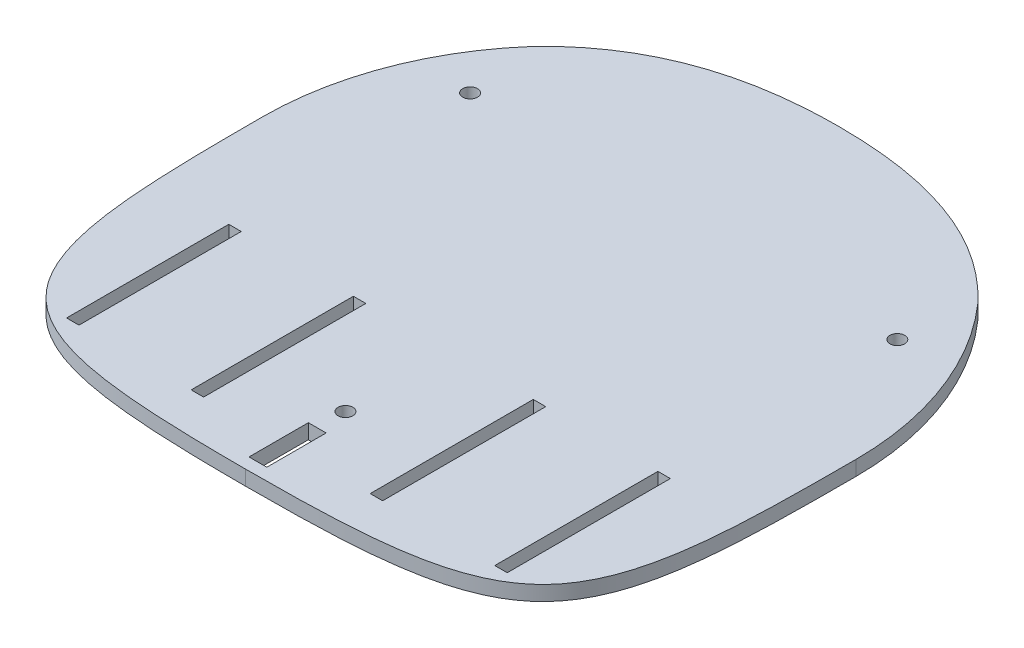
SolidWorks part; units mm, degrees
ref_plane "Front Plane" through (0, 0, 0) normal (0, 0, 1) x (1, 0, 0)
ref_plane "Top Plane" through (0, 0, 0) normal (0, 1, 0) x (1, 0, 0)
ref_plane "Right Plane" through (0, 0, 0) normal (1, 0, 0) x (0, 0, -1)
sketch "Layer1Limits" plane through (0, 0, 0) normal (0, 1, 0) x (1, 0, 0)
  line L0 (-127, 119.8228) -> (127, -134.1772) construction
  line L1 (-127, -134.1772) -> (127, -134.1772) construction
  line L2 (-127, -134.1772) -> (-127, 119.8228) construction
  line L3 (-127, 119.8228) -> (127, 119.8228) construction
  line L4 (127, -134.1772) -> (127, 119.8228) construction
  line L5 (127, 119.8228) -> (-127, -134.1772) construction
  line L6 (0, -1000) -> (0, 49000) construction
  point P4 (0, -7.1772)
  dimension "D1" = 254
  dimension "D2" = 254
sketch "Sketch1" plane through (0, 0, 0) normal (0, 1, 0) x (1, 0, 0)
  line L0 (0, 0) -> (-157.9039, -157.9039) construction
  line L1 (0, -134.1772) -> (0, 127) construction
  line L2 (-127, -134.1772) -> (127, -134.1772) construction
  arc A0 (127, 0) -> (-127, 0) centre (0, 0) ccw
  spline S0 degree 3 poles (-127, 0) (-127, -50.6247) (-125.8471, -127.4032) (-59.0891, -134.1772) (0, -134.1772) knots 0 0 0 0 0.496988 1 1 1 1
  spline S1 degree 3 poles (127, 0) (127, -50.6247) (125.8471, -127.4032) (59.0891, -134.1772) (0, -134.1772) knots 0 0 0 0 0.496988 1 1 1 1
  dimension "D1" = 254
extrude "Base" add sketch "Sketch1" along normal blind 6.35
sketch "Sketch16" plane through (0, 6.35, 0) normal (0, 1, 0) x (1, 0, 0)
  line L0 (0, -1000) -> (0, 49000) construction
  line L1 (-95.2696, 133.35) -> (-95.2696, 83.9803)
  line L2 (-95.2696, 133.35) -> (95.2696, 133.35)
  line L3 (95.2696, 133.35) -> (95.2696, 83.9803)
  arc A0 (127, 0) -> (-127, 0) centre (0, 0) ccw construction
  spline S0 degree 3 poles (-95.2696, 83.9803) (-69.156, 111.7112) (-34.9729, 119.8228) (0, 119.8228) knots 0 0 0 0 1 1 1 1
  spline S1 degree 3 poles (95.2696, 83.9803) (69.156, 111.7112) (34.9729, 119.8228) (0, 119.8228) knots 0 0 0 0 1 1 1 1
extrude "EmptySpaceTrim" cut sketch "Sketch16" against normal through all
sketch "ShaftLayout" plane through (0, 6.35, 0) normal (0, 1, 0) x (1, 0, 0)
  line L0 (-127, 0) -> (127, 0) construction
  line L1 (0, 133.35) -> (0, -127) construction
  line L2 (-114.7053, -6.35) -> (-104.7993, -6.35)
  line L3 (-36.3853, -38) -> (-94.3853, -38)
  line L4 (-36.3853, -38) -> (-36.3853, 38)
  line L5 (-36.3853, 38) -> (-94.3853, 38)
  line L6 (-94.3853, -38) -> (-94.3853, 38)
  line L7 (-36.3853, -38) -> (-94.3853, 38) construction
  line L8 (-36.3853, 38) -> (-94.3853, -38) construction
  line L9 (-102.0053, -15.875) -> (-104.7993, -15.875)
  line L10 (-102.0053, -15.875) -> (-102.0053, 15.875)
  line L11 (-102.0053, 15.875) -> (-104.7993, 15.875)
  line L12 (-104.7993, -15.875) -> (-104.7993, 15.875)
  line L13 (-102.0053, -15.875) -> (-104.7993, 15.875) construction
  line L14 (-102.0053, 15.875) -> (-104.7993, -15.875) construction
  line L15 (-114.7053, -6.35) -> (-114.7053, 6.35)
  line L16 (-104.7993, -6.35) -> (-104.7993, 6.35)
  line L17 (-114.7053, 6.35) -> (-104.7993, 6.35)
  line L18 (-114.7053, -6.35) -> (-104.7993, 6.35) construction
  line L19 (-104.7993, -6.35) -> (-114.7053, 6.35) construction
  line L20 (-116.2928, -9.525) -> (-114.7053, -9.525)
  line L21 (-116.2928, -9.525) -> (-116.2928, 9.525)
  line L22 (-114.7053, -9.525) -> (-114.7053, 9.525)
  line L23 (-116.2928, 9.525) -> (-114.7053, 9.525)
  line L24 (-116.2928, -9.525) -> (-114.7053, 9.525) construction
  line L25 (-114.7053, -9.525) -> (-116.2928, 9.525) construction
  line L26 (-127.4053, -7.9375) -> (-116.2928, -7.9375)
  line L27 (-127.4053, -7.9375) -> (-127.4053, 7.9375)
  line L28 (-116.2928, -7.9375) -> (-116.2928, 7.9375)
  line L29 (-127.4053, 7.9375) -> (-116.2928, 7.9375)
  line L30 (-127.4053, -7.9375) -> (-116.2928, 7.9375) construction
  line L31 (-116.2928, -7.9375) -> (-127.4053, 7.9375) construction
  line L32 (-17.3353, -7.9375) -> (-28.4478, -7.9375)
  line L33 (-30.0353, -9.525) -> (-28.4478, -9.525)
  line L34 (-30.0353, -9.525) -> (-30.0353, 9.525)
  line L35 (-30.0353, 9.525) -> (-28.4478, 9.525)
  line L36 (-28.4478, -9.525) -> (-28.4478, 9.525)
  line L37 (-30.0353, -9.525) -> (-28.4478, 9.525) construction
  line L38 (-30.0353, 9.525) -> (-28.4478, -9.525) construction
  line L39 (-17.3353, -7.9375) -> (-17.3353, 7.9375)
  line L40 (-28.4478, -7.9375) -> (-28.4478, 7.9375)
  line L41 (-17.3353, 7.9375) -> (-28.4478, 7.9375)
  line L42 (-17.3353, -7.9375) -> (-28.4478, 7.9375) construction
  line L43 (-28.4478, -7.9375) -> (-17.3353, 7.9375) construction
  line L45 (-67.3853, -10.033) -> (-56.3853, -10.033)
  line L46 (-67.3853, -10.033) -> (-67.3853, 10.033)
  line L47 (-67.3853, 10.033) -> (-56.3853, 10.033)
  line L48 (-56.3853, -10.033) -> (-56.3853, 10.033)
  line L49 (-67.3853, -10.033) -> (-56.3853, 10.033) construction
  line L50 (-67.3853, 10.033) -> (-56.3853, -10.033) construction
  point P10 (-65.3853, 0)
  point P15 (-103.4023, 0)
  point P20 (-29.2416, 0)
  point P21 (-109.7523, 0)
  point P22 (-115.4991, 0)
  point P23 (-121.8491, 0)
  point P40 (-61.8853, 0)
  point P41 (-22.8916, 0)
  dimension "D1" = 58
  dimension "D2" = 76
  dimension "D3" = 7.62
  dimension "D4" = 2.794
  dimension "D5" = 31.75
  dimension "D6" = 9.906
  dimension "D7" = 12.7
  dimension "D8" = 19.05
  dimension "D9" = 1.5875
  dimension "D10" = 12.7
  dimension "D11" = 15.875
  dimension "D12" = 19.05
  dimension "D13" = 1.5875
  dimension "D14" = 15.875
  dimension "D15" = 12.7
  dimension "D16" = 6.35
  dimension "D17" = 20.066
  dimension "D18" = 20
  dimension "D19" = 11
sketch "MotorLayout" plane through (0, 6.35, 0) normal (0, 1, 0) x (1, 0, 0)
  line L0 (-94.3853, -81.74) -> (-114.3853, -81.74) construction
  line L1 (-94.3853, -110.24) -> (-18.3853, -110.24)
  line L2 (-94.3853, -110.24) -> (-94.3853, -53.24)
  line L3 (-94.3853, -53.24) -> (-18.3853, -53.24)
  line L4 (-18.3853, -110.24) -> (-18.3853, -53.24)
  line L5 (-94.3853, -110.24) -> (-18.3853, -53.24) construction
  line L6 (-94.3853, -53.24) -> (-18.3853, -110.24) construction
  line L7 (-114.7053, -92.0587) -> (-104.7993, -92.0587)
  line L8 (-104.7993, -97.615) -> (-102.0053, -97.615)
  line L9 (-104.7993, -97.615) -> (-104.7993, -65.865)
  line L10 (-104.7993, -65.865) -> (-102.0053, -65.865)
  line L11 (-102.0053, -97.615) -> (-102.0053, -65.865)
  line L12 (-104.7993, -97.615) -> (-102.0053, -65.865) construction
  line L13 (-104.7993, -65.865) -> (-102.0053, -97.615) construction
  line L14 (-36.3853, -38) -> (-94.3853, -38) construction
  line L15 (-114.7053, -92.0587) -> (-114.7053, -71.4212)
  line L16 (-104.7993, -92.0587) -> (-104.7993, -71.4212)
  line L17 (-114.7053, -71.4212) -> (-104.7993, -71.4212)
  line L18 (-114.7053, -92.0587) -> (-104.7993, -71.4212) construction
  line L19 (-104.7993, -92.0587) -> (-114.7053, -71.4212) construction
  line L20 (-103.4023, -1000) -> (-103.4023, 49000) construction
  line L21 (-34.8953, -53.24) -> (-34.8953, -110.24) construction
  point P0 (-56.3853, -81.74)
  point P7 (-103.4023, -81.74)
  point P14 (-109.7523, -81.74)
  dimension "D1" = 20
  dimension "D2" = 76
  dimension "D3" = 57
  dimension "D4" = 2.794
  dimension "D5" = 15.24
  dimension "D6" = 31.75
  dimension "D7" = 20.6375
  dimension "D8" = 12.7
  dimension "D9" = 7.62
  dimension "D10" = 16.51
sketch "Sketch8" plane through (0, 6.35, 0) normal (0, 1, 0) x (1, 0, 0)
  line L0 (-94.3853, -81.74) -> (-18.3853, -81.74) construction
  line L1 (-18.3853, -110.24) -> (-18.3853, -53.24) construction
  line L2 (-94.3853, -53.24) -> (-18.3853, -53.24) construction
  line L3 (-35.7113, -116.463) -> (-41.0453, -116.463)
  line L4 (-35.7113, -116.463) -> (-35.7113, -47.017)
  line L5 (-35.7113, -47.017) -> (-41.0453, -47.017)
  line L6 (-41.0453, -116.463) -> (-41.0453, -47.017)
  line L7 (-35.7113, -116.463) -> (-41.0453, -47.017) construction
  line L8 (-35.7113, -47.017) -> (-41.0453, -116.463) construction
  line L9 (0, -1000) -> (0, 49000) construction
  line L10 (-94.3853, -110.24) -> (-18.3853, -110.24) construction
  line L11 (-3.81, -128.9302) -> (3.81, -128.9302)
  line L12 (89.0513, -46.763) -> (94.3853, -116.59) construction
  line L13 (89.0513, -116.59) -> (94.3853, -46.763) construction
  line L14 (35.7113, -46.763) -> (41.0453, -116.59) construction
  line L15 (-89.0513, -116.463) -> (-94.3853, -116.463)
  line L16 (-89.0513, -116.463) -> (-89.0513, -47.017)
  line L17 (-89.0513, -47.017) -> (-94.3853, -47.017)
  line L18 (-94.3853, -116.463) -> (-94.3853, -47.017)
  line L19 (-89.0513, -116.463) -> (-94.3853, -47.017) construction
  line L20 (-89.0513, -47.017) -> (-94.3853, -116.463) construction
  line L21 (-94.3853, -110.24) -> (-94.3853, -53.24) construction
  line L22 (-3.81, -128.9302) -> (-3.81, -103.5302)
  line L23 (35.7113, -116.59) -> (41.0453, -46.763) construction
  line L24 (-3.81, -103.5302) -> (3.81, -103.5302)
  line L25 (3.81, -128.9302) -> (3.81, -103.5302)
  line L26 (-3.81, -128.9302) -> (3.81, -103.5302) construction
  line L27 (-3.81, -103.5302) -> (3.81, -128.9302) construction
  line L29 (94.3853, -116.59) -> (94.3853, -46.763)
  line L30 (89.0513, -46.763) -> (94.3853, -46.763)
  line L31 (89.0513, -116.59) -> (89.0513, -46.763)
  line L32 (89.0513, -116.59) -> (94.3853, -116.59)
  line L33 (41.0453, -116.59) -> (41.0453, -46.763)
  line L34 (35.7113, -46.763) -> (41.0453, -46.763)
  line L35 (35.7113, -116.59) -> (35.7113, -46.763)
  line L36 (35.7113, -116.59) -> (41.0453, -116.59)
  point P6 (-63.7079, -81.74)
  point P7 (-38.2513, -81.74)
  point P16 (0, -116.2302)
  point P19 (-91.5913, -81.74)
  point P39 (91.5913, -81.74)
  point P40 (38.2513, -81.74)
  dimension "D1" = 5.334
  dimension "D2" = 6.223
  dimension "D4" = 7.62
  dimension "D5" = 25.4
  dimension "D6" = 6.223
  dimension "D3" = 2
extrude "MotorCut" cut sketch "Sketch8" against normal through all
sketch "Sketch11" plane through (0, 6.35, 0) normal (0, 1, 0) x (1, 0, 0)
  line L0 (0, -1000) -> (0, 49000) construction
  line L1 (-127, 0) -> (127, 0) construction
  circle A1 centre (0, -91.44) radius 3.175
  circle A2 centre (-91.44, 53.34) radius 3.175
  circle A3 centre (91.44, 53.34) radius 3.175
  dimension "D1" = 6.35
  dimension "D2" = 91.44
  dimension "D3" = 6.35
  dimension "D6" = 91.44
  dimension "D4" = 53.34
extrude "ScrewCut" cut sketch "Sketch11" against normal through all
sketch "Sketch17" plane through (0, 6.35, 0) normal (0, 1, 0) x (1, 0, 0)
  line L0 (-94.3853, -47.017) -> (-94.3853, -116.463) construction
  line L1 (94.3853, -116.59) -> (94.3853, -46.763) construction
  line L2 (-112.1653, -34.317) -> (112.1653, -34.317) construction
  line L3 (-112.1653, -34.317) -> (-112.1653, 40.64) construction
  line L4 (-112.1653, 40.64) -> (112.1653, 40.64) construction
  line L5 (112.1653, -34.317) -> (112.1653, 40.64) construction
  line L6 (-112.1653, -34.317) -> (-99.4653, -34.317) construction
  line L7 (-112.1653, -33.5232) -> (-99.4653, -33.5232)
  line L8 (-112.1653, -35.1107) -> (-99.4653, -35.1107)
  line L9 (-88.6508, -34.3253) -> (-75.9508, -34.3253) construction
  line L10 (-88.6508, -33.5315) -> (-75.9508, -33.5315)
  line L11 (-88.6508, -35.119) -> (-75.9508, -35.119)
  line L12 (-65.1363, -34.3336) -> (-52.4363, -34.3336) construction
  line L13 (-65.1363, -33.5398) -> (-52.4363, -33.5398)
  line L14 (-65.1363, -35.1273) -> (-52.4363, -35.1273)
  line L15 (-41.6218, -34.3419) -> (-28.9218, -34.3419) construction
  line L16 (-41.6218, -33.5481) -> (-28.9218, -33.5481)
  line L17 (-41.6218, -35.1356) -> (-28.9218, -35.1356)
  line L18 (-18.1073, -34.3502) -> (-5.4073, -34.3502) construction
  line L19 (-18.1073, -33.5564) -> (-5.4073, -33.5564)
  line L20 (-18.1073, -35.1439) -> (-5.4073, -35.1439)
  line L21 (5.4073, -34.3584) -> (18.1073, -34.3584) construction
  line L22 (5.4073, -33.5647) -> (18.1073, -33.5647)
  line L23 (5.4073, -35.1522) -> (18.1073, -35.1522)
  line L24 (28.9218, -34.3667) -> (41.6218, -34.3667) construction
  line L25 (28.9218, -33.573) -> (41.6218, -33.573)
  line L26 (28.9218, -35.1605) -> (41.6218, -35.1605)
  line L27 (52.4363, -34.375) -> (65.1363, -34.375) construction
  line L28 (52.4363, -33.5813) -> (65.1363, -33.5813)
  line L29 (52.4363, -35.1688) -> (65.1363, -35.1688)
  line L30 (75.9508, -34.3833) -> (88.6508, -34.3833) construction
  line L31 (75.9508, -33.5896) -> (88.6508, -33.5896)
  line L32 (75.9508, -35.1771) -> (88.6508, -35.1771)
  line L33 (99.4653, -34.3916) -> (112.1653, -34.3916) construction
  line L34 (99.4653, -33.5978) -> (112.1653, -33.5978)
  line L35 (99.4653, -35.1854) -> (112.1653, -35.1854)
  line L36 (-88.6508, -23.6065) -> (-75.9508, -23.6065) construction
  line L37 (-88.6508, -22.8127) -> (-75.9508, -22.8127)
  line L38 (-88.6508, -24.4002) -> (-75.9508, -24.4002)
  line L39 (-65.1363, -23.6148) -> (-52.4363, -23.6148) construction
  line L40 (-65.1363, -22.821) -> (-52.4363, -22.821)
  line L41 (-65.1363, -24.4085) -> (-52.4363, -24.4085)
  line L42 (-41.6218, -23.6231) -> (-28.9218, -23.6231) construction
  line L43 (-41.6218, -22.8293) -> (-28.9218, -22.8293)
  line L44 (-41.6218, -24.4168) -> (-28.9218, -24.4168)
  line L45 (-18.1073, -23.6314) -> (-5.4073, -23.6314) construction
  line L46 (-18.1073, -22.8376) -> (-5.4073, -22.8376)
  line L47 (-18.1073, -24.4251) -> (-5.4073, -24.4251)
  line L48 (5.4073, -23.6396) -> (18.1073, -23.6396) construction
  line L49 (5.4073, -22.8459) -> (18.1073, -22.8459)
  line L50 (5.4073, -24.4334) -> (18.1073, -24.4334)
  line L51 (28.9218, -23.6479) -> (41.6218, -23.6479) construction
  line L52 (28.9218, -22.8542) -> (41.6218, -22.8542)
  line L53 (28.9218, -24.4417) -> (41.6218, -24.4417)
  line L54 (52.4363, -23.6562) -> (65.1363, -23.6562) construction
  line L55 (52.4363, -22.8625) -> (65.1363, -22.8625)
  line L56 (52.4363, -24.45) -> (65.1363, -24.45)
  line L57 (75.9508, -23.6645) -> (88.6508, -23.6645) construction
  line L58 (75.9508, -22.8708) -> (88.6508, -22.8708)
  line L59 (75.9508, -24.4583) -> (88.6508, -24.4583)
  line L60 (99.4653, -23.6728) -> (112.1653, -23.6728) construction
  line L61 (99.4653, -22.879) -> (112.1653, -22.879)
  line L62 (99.4653, -24.4666) -> (112.1653, -24.4666)
  line L63 (-88.6508, -12.8877) -> (-75.9508, -12.8877) construction
  line L64 (-88.6508, -12.0939) -> (-75.9508, -12.0939)
  line L65 (-88.6508, -13.6814) -> (-75.9508, -13.6814)
  line L66 (-65.1363, -12.896) -> (-52.4363, -12.896) construction
  line L67 (-65.1363, -12.1022) -> (-52.4363, -12.1022)
  line L68 (-65.1363, -13.6897) -> (-52.4363, -13.6897)
  line L69 (-41.6218, -12.9043) -> (-28.9218, -12.9043) construction
  line L70 (-41.6218, -12.1105) -> (-28.9218, -12.1105)
  line L71 (-41.6218, -13.698) -> (-28.9218, -13.698)
  line L72 (-18.1073, -12.9126) -> (-5.4073, -12.9126) construction
  line L73 (-18.1073, -12.1188) -> (-5.4073, -12.1188)
  line L74 (-18.1073, -13.7063) -> (-5.4073, -13.7063)
  line L75 (5.4073, -12.9208) -> (18.1073, -12.9208) construction
  line L76 (5.4073, -12.1271) -> (18.1073, -12.1271)
  line L77 (5.4073, -13.7146) -> (18.1073, -13.7146)
  line L78 (28.9218, -12.9291) -> (41.6218, -12.9291) construction
  line L79 (28.9218, -12.1354) -> (41.6218, -12.1354)
  line L80 (28.9218, -13.7229) -> (41.6218, -13.7229)
  line L81 (52.4363, -12.9374) -> (65.1363, -12.9374) construction
  line L82 (52.4363, -12.1437) -> (65.1363, -12.1437)
  line L83 (52.4363, -13.7312) -> (65.1363, -13.7312)
  line L84 (75.9508, -12.9457) -> (88.6508, -12.9457) construction
  line L85 (75.9508, -12.152) -> (88.6508, -12.152)
  line L86 (75.9508, -13.7395) -> (88.6508, -13.7395)
  line L87 (99.4653, -12.954) -> (112.1653, -12.954) construction
  line L88 (99.4653, -12.1602) -> (112.1653, -12.1602)
  line L89 (99.4653, -13.7478) -> (112.1653, -13.7478)
  line L90 (-88.6508, -2.1689) -> (-75.9508, -2.1689) construction
  line L91 (-88.6508, -1.3751) -> (-75.9508, -1.3751)
  line L92 (-88.6508, -2.9626) -> (-75.9508, -2.9626)
  line L93 (-65.1363, -2.1772) -> (-52.4363, -2.1772) construction
  line L94 (-65.1363, -1.3834) -> (-52.4363, -1.3834)
  line L95 (-65.1363, -2.9709) -> (-52.4363, -2.9709)
  line L96 (-41.6218, -2.1855) -> (-28.9218, -2.1855) construction
  line L97 (-41.6218, -1.3917) -> (-28.9218, -1.3917)
  line L98 (-41.6218, -2.9792) -> (-28.9218, -2.9792)
  line L99 (-18.1073, -2.1938) -> (-5.4073, -2.1938) construction
  line L100 (-18.1073, -1.4) -> (-5.4073, -1.4)
  line L101 (-18.1073, -2.9875) -> (-5.4073, -2.9875)
  line L102 (5.4073, -2.202) -> (18.1073, -2.202) construction
  line L103 (5.4073, -1.4083) -> (18.1073, -1.4083)
  line L104 (5.4073, -2.9958) -> (18.1073, -2.9958)
  line L105 (28.9218, -2.2103) -> (41.6218, -2.2103) construction
  line L106 (28.9218, -1.4166) -> (41.6218, -1.4166)
  line L107 (28.9218, -3.0041) -> (41.6218, -3.0041)
  line L108 (52.4363, -2.2186) -> (65.1363, -2.2186) construction
  line L109 (52.4363, -1.4249) -> (65.1363, -1.4249)
  line L110 (52.4363, -3.0124) -> (65.1363, -3.0124)
  line L111 (75.9508, -2.2269) -> (88.6508, -2.2269) construction
  line L112 (75.9508, -1.4332) -> (88.6508, -1.4332)
  line L113 (75.9508, -3.0207) -> (88.6508, -3.0207)
  line L114 (99.4653, -2.2352) -> (112.1653, -2.2352) construction
  line L115 (99.4653, -1.4414) -> (112.1653, -1.4414)
  line L116 (99.4653, -3.029) -> (112.1653, -3.029)
  line L117 (-88.6508, 8.5499) -> (-75.9508, 8.5499) construction
  line L118 (-88.6508, 9.3437) -> (-75.9508, 9.3437)
  line L119 (-88.6508, 7.7562) -> (-75.9508, 7.7562)
  line L120 (-65.1363, 8.5416) -> (-52.4363, 8.5416) construction
  line L121 (-65.1363, 9.3354) -> (-52.4363, 9.3354)
  line L122 (-65.1363, 7.7479) -> (-52.4363, 7.7479)
  line L123 (-41.6218, 8.5333) -> (-28.9218, 8.5333) construction
  line L124 (-41.6218, 9.3271) -> (-28.9218, 9.3271)
  line L125 (-41.6218, 7.7396) -> (-28.9218, 7.7396)
  line L126 (-18.1073, 8.525) -> (-5.4073, 8.525) construction
  line L127 (-18.1073, 9.3188) -> (-5.4073, 9.3188)
  line L128 (-18.1073, 7.7313) -> (-5.4073, 7.7313)
  line L129 (5.4073, 8.5168) -> (18.1073, 8.5168) construction
  line L130 (5.4073, 9.3105) -> (18.1073, 9.3105)
  line L131 (5.4073, 7.723) -> (18.1073, 7.723)
  line L132 (28.9218, 8.5085) -> (41.6218, 8.5085) construction
  line L133 (28.9218, 9.3022) -> (41.6218, 9.3022)
  line L134 (28.9218, 7.7147) -> (41.6218, 7.7147)
  line L135 (52.4363, 8.5002) -> (65.1363, 8.5002) construction
  line L136 (52.4363, 9.2939) -> (65.1363, 9.2939)
  line L137 (52.4363, 7.7064) -> (65.1363, 7.7064)
  line L138 (75.9508, 8.4919) -> (88.6508, 8.4919) construction
  line L139 (75.9508, 9.2856) -> (88.6508, 9.2856)
  line L140 (75.9508, 7.6981) -> (88.6508, 7.6981)
  line L141 (99.4653, 8.4836) -> (112.1653, 8.4836) construction
  line L142 (99.4653, 9.2774) -> (112.1653, 9.2774)
  line L143 (99.4653, 7.6898) -> (112.1653, 7.6898)
  line L144 (-88.6508, 19.2687) -> (-75.9508, 19.2687) construction
  line L145 (-88.6508, 20.0625) -> (-75.9508, 20.0625)
  line L146 (-88.6508, 18.475) -> (-75.9508, 18.475)
  line L147 (-65.1363, 19.2604) -> (-52.4363, 19.2604) construction
  line L148 (-65.1363, 20.0542) -> (-52.4363, 20.0542)
  line L149 (-65.1363, 18.4667) -> (-52.4363, 18.4667)
  line L150 (-41.6218, 19.2521) -> (-28.9218, 19.2521) construction
  line L151 (-41.6218, 20.0459) -> (-28.9218, 20.0459)
  line L152 (-41.6218, 18.4584) -> (-28.9218, 18.4584)
  line L153 (-18.1073, 19.2438) -> (-5.4073, 19.2438) construction
  line L154 (-18.1073, 20.0376) -> (-5.4073, 20.0376)
  line L155 (-18.1073, 18.4501) -> (-5.4073, 18.4501)
  line L156 (5.4073, 19.2356) -> (18.1073, 19.2356) construction
  line L157 (5.4073, 20.0293) -> (18.1073, 20.0293)
  line L158 (5.4073, 18.4418) -> (18.1073, 18.4418)
  line L159 (28.9218, 19.2273) -> (41.6218, 19.2273) construction
  line L160 (28.9218, 20.021) -> (41.6218, 20.021)
  line L161 (28.9218, 18.4335) -> (41.6218, 18.4335)
  line L162 (52.4363, 19.219) -> (65.1363, 19.219) construction
  line L163 (52.4363, 20.0127) -> (65.1363, 20.0127)
  line L164 (52.4363, 18.4252) -> (65.1363, 18.4252)
  line L165 (75.9508, 19.2107) -> (88.6508, 19.2107) construction
  line L166 (75.9508, 20.0044) -> (88.6508, 20.0044)
  line L167 (75.9508, 18.4169) -> (88.6508, 18.4169)
  line L168 (99.4653, 19.2024) -> (112.1653, 19.2024) construction
  line L169 (99.4653, 19.9962) -> (112.1653, 19.9962)
  line L170 (99.4653, 18.4086) -> (112.1653, 18.4086)
  line L171 (-88.6508, 29.9875) -> (-75.9508, 29.9875) construction
  line L172 (-88.6508, 30.7813) -> (-75.9508, 30.7813)
  line L173 (-88.6508, 29.1938) -> (-75.9508, 29.1938)
  line L174 (-65.1363, 29.9792) -> (-52.4363, 29.9792) construction
  line L175 (-65.1363, 30.773) -> (-52.4363, 30.773)
  line L176 (-65.1363, 29.1855) -> (-52.4363, 29.1855)
  line L177 (-41.6218, 29.9709) -> (-28.9218, 29.9709) construction
  line L178 (-41.6218, 30.7647) -> (-28.9218, 30.7647)
  line L179 (-41.6218, 29.1772) -> (-28.9218, 29.1772)
  line L180 (-18.1073, 29.9626) -> (-5.4073, 29.9626) construction
  line L181 (-18.1073, 30.7564) -> (-5.4073, 30.7564)
  line L182 (-18.1073, 29.1689) -> (-5.4073, 29.1689)
  line L183 (5.4073, 29.9544) -> (18.1073, 29.9544) construction
  line L184 (5.4073, 30.7481) -> (18.1073, 30.7481)
  line L185 (5.4073, 29.1606) -> (18.1073, 29.1606)
  line L186 (28.9218, 29.9461) -> (41.6218, 29.9461) construction
  line L187 (28.9218, 30.7398) -> (41.6218, 30.7398)
  line L188 (28.9218, 29.1523) -> (41.6218, 29.1523)
  line L189 (52.4363, 29.9378) -> (65.1363, 29.9378) construction
  line L190 (52.4363, 30.7315) -> (65.1363, 30.7315)
  line L191 (52.4363, 29.144) -> (65.1363, 29.144)
  line L192 (75.9508, 29.9295) -> (88.6508, 29.9295) construction
  line L193 (75.9508, 30.7232) -> (88.6508, 30.7232)
  line L194 (75.9508, 29.1357) -> (88.6508, 29.1357)
  line L195 (99.4653, 29.9212) -> (112.1653, 29.9212) construction
  line L196 (99.4653, 30.715) -> (112.1653, 30.715)
  line L197 (99.4653, 29.1274) -> (112.1653, 29.1274)
  line L198 (-88.6508, 40.7063) -> (-75.9508, 40.7063) construction
  line L199 (-88.6508, 41.5001) -> (-75.9508, 41.5001)
  line L200 (-88.6508, 39.9126) -> (-75.9508, 39.9126)
  line L201 (-65.1363, 40.698) -> (-52.4363, 40.698) construction
  line L202 (-65.1363, 41.4918) -> (-52.4363, 41.4918)
  line L203 (-65.1363, 39.9043) -> (-52.4363, 39.9043)
  line L204 (-41.6218, 40.6897) -> (-28.9218, 40.6897) construction
  line L205 (-41.6218, 41.4835) -> (-28.9218, 41.4835)
  line L206 (-41.6218, 39.896) -> (-28.9218, 39.896)
  line L207 (-18.1073, 40.6814) -> (-5.4073, 40.6814) construction
  line L208 (-18.1073, 41.4752) -> (-5.4073, 41.4752)
  line L209 (-18.1073, 39.8877) -> (-5.4073, 39.8877)
  line L210 (5.4073, 40.6732) -> (18.1073, 40.6732) construction
  line L211 (5.4073, 41.4669) -> (18.1073, 41.4669)
  line L212 (5.4073, 39.8794) -> (18.1073, 39.8794)
  line L213 (28.9218, 40.6649) -> (41.6218, 40.6649) construction
  line L214 (28.9218, 41.4586) -> (41.6218, 41.4586)
  line L215 (28.9218, 39.8711) -> (41.6218, 39.8711)
  line L216 (52.4363, 40.6566) -> (65.1363, 40.6566) construction
  line L217 (52.4363, 41.4503) -> (65.1363, 41.4503)
  line L218 (52.4363, 39.8628) -> (65.1363, 39.8628)
  line L219 (75.9508, 40.6483) -> (88.6508, 40.6483) construction
  line L220 (75.9508, 41.442) -> (88.6508, 41.442)
  line L221 (75.9508, 39.8545) -> (88.6508, 39.8545)
  line L222 (99.4653, 40.64) -> (112.1653, 40.64) construction
  line L223 (99.4653, 41.4337) -> (112.1653, 41.4337)
  line L224 (99.4653, 39.8462) -> (112.1653, 39.8462)
  line L225 (-112.1653, -23.5982) -> (-99.4653, -23.5982) construction
  line L226 (-112.1653, -22.8044) -> (-99.4653, -22.8044)
  line L227 (-112.1653, -24.3919) -> (-99.4653, -24.3919)
  line L228 (-112.1653, -12.8794) -> (-99.4653, -12.8794) construction
  line L229 (-112.1653, -12.0856) -> (-99.4653, -12.0856)
  line L230 (-112.1653, -13.6731) -> (-99.4653, -13.6731)
  line L231 (-112.1653, -2.1606) -> (-99.4653, -2.1606) construction
  line L232 (-112.1653, -1.3668) -> (-99.4653, -1.3668)
  line L233 (-112.1653, -2.9543) -> (-99.4653, -2.9543)
  line L234 (-112.1653, 8.5582) -> (-99.4653, 8.5582) construction
  line L235 (-112.1653, 9.352) -> (-99.4653, 9.352)
  line L236 (-112.1653, 7.7645) -> (-99.4653, 7.7645)
  line L237 (-112.1653, 19.277) -> (-99.4653, 19.277) construction
  line L238 (-112.1653, 20.0708) -> (-99.4653, 20.0708)
  line L239 (-112.1653, 18.4833) -> (-99.4653, 18.4833)
  line L240 (-112.1653, 29.9958) -> (-99.4653, 29.9958) construction
  line L241 (-112.1653, 30.7896) -> (-99.4653, 30.7896)
  line L242 (-112.1653, 29.2021) -> (-99.4653, 29.2021)
  line L243 (-112.1653, 40.7146) -> (-99.4653, 40.7146) construction
  line L244 (-112.1653, 41.5084) -> (-99.4653, 41.5084)
  line L245 (-112.1653, 39.9209) -> (-99.4653, 39.9209)
  line L246 (-65.1363, 53.0043) -> (-52.4363, 53.0043) construction
  line L247 (-65.1363, 53.7981) -> (-52.4363, 53.7981)
  line L248 (-65.1363, 52.2106) -> (-52.4363, 52.2106)
  line L249 (65.1363, -959.3434) -> (65.1363, 49040.6566) construction
  line L250 (-41.6218, 53.0963) -> (-28.9218, 53.0963) construction
  line L251 (-41.6218, 53.89) -> (-28.9218, 53.89)
  line L252 (-41.6218, 52.3025) -> (-28.9218, 52.3025)
  line L253 (-18.1073, 53.1882) -> (-5.4073, 53.1882) construction
  line L254 (-18.1073, 53.982) -> (-5.4073, 53.982)
  line L255 (-18.1073, 52.3945) -> (-5.4073, 52.3945)
  line L256 (5.4073, 53.2802) -> (18.1073, 53.2802) construction
  line L257 (5.4073, 54.0739) -> (18.1073, 54.0739)
  line L258 (5.4073, 52.4864) -> (18.1073, 52.4864)
  line L259 (28.9218, 53.3721) -> (41.6218, 53.3721) construction
  line L260 (28.9218, 54.1659) -> (41.6218, 54.1659)
  line L261 (28.9218, 52.5784) -> (41.6218, 52.5784)
  line L262 (52.4363, 53.4641) -> (65.1363, 53.4641) construction
  line L263 (52.4363, 54.2578) -> (65.1363, 54.2578)
  line L264 (52.4363, 52.6703) -> (65.1363, 52.6703)
  line L265 (-41.6218, 63.8151) -> (-28.9218, 63.8151) construction
  line L266 (-41.6218, 64.6088) -> (-28.9218, 64.6088)
  line L267 (-41.6218, 63.0213) -> (-28.9218, 63.0213)
  line L268 (-18.1073, 63.907) -> (-5.4073, 63.907) construction
  line L269 (-18.1073, 64.7008) -> (-5.4073, 64.7008)
  line L270 (-18.1073, 63.1133) -> (-5.4073, 63.1133)
  line L271 (5.4073, 63.999) -> (18.1073, 63.999) construction
  line L272 (5.4073, 64.7927) -> (18.1073, 64.7927)
  line L273 (5.4073, 63.2052) -> (18.1073, 63.2052)
  line L274 (28.9218, 64.0909) -> (41.6218, 64.0909) construction
  line L275 (28.9218, 64.8847) -> (41.6218, 64.8847)
  line L276 (28.9218, 63.2972) -> (41.6218, 63.2972)
  line L277 (52.4363, 64.1829) -> (65.1363, 64.1829) construction
  line L278 (52.4363, 64.9766) -> (65.1363, 64.9766)
  line L279 (52.4363, 63.3891) -> (65.1363, 63.3891)
  line L280 (-41.6218, 74.5339) -> (-28.9218, 74.5339) construction
  line L281 (-41.6218, 75.3276) -> (-28.9218, 75.3276)
  line L282 (-41.6218, 73.7401) -> (-28.9218, 73.7401)
  line L283 (-18.1073, 74.6258) -> (-5.4073, 74.6258) construction
  line L284 (-18.1073, 75.4196) -> (-5.4073, 75.4196)
  line L285 (-18.1073, 73.8321) -> (-5.4073, 73.8321)
  line L286 (5.4073, 74.7178) -> (18.1073, 74.7178) construction
  line L287 (5.4073, 75.5115) -> (18.1073, 75.5115)
  line L288 (5.4073, 73.924) -> (18.1073, 73.924)
  line L289 (28.9218, 74.8097) -> (41.6218, 74.8097) construction
  line L290 (28.9218, 75.6035) -> (41.6218, 75.6035)
  line L291 (28.9218, 74.016) -> (41.6218, 74.016)
  line L292 (52.4363, 74.9017) -> (65.1363, 74.9017) construction
  line L293 (52.4363, 75.6954) -> (65.1363, 75.6954)
  line L294 (52.4363, 74.1079) -> (65.1363, 74.1079)
  line L295 (-41.6218, 85.2527) -> (-28.9218, 85.2527) construction
  line L296 (-41.6218, 86.0464) -> (-28.9218, 86.0464)
  line L297 (-41.6218, 84.4589) -> (-28.9218, 84.4589)
  line L298 (-18.1073, 85.3446) -> (-5.4073, 85.3446) construction
  line L299 (-18.1073, 86.1384) -> (-5.4073, 86.1384)
  line L300 (-18.1073, 84.5509) -> (-5.4073, 84.5509)
  line L301 (5.4073, 85.4366) -> (18.1073, 85.4366) construction
  line L302 (5.4073, 86.2303) -> (18.1073, 86.2303)
  line L303 (5.4073, 84.6428) -> (18.1073, 84.6428)
  line L304 (28.9218, 85.5285) -> (41.6218, 85.5285) construction
  line L305 (28.9218, 86.3223) -> (41.6218, 86.3223)
  line L306 (28.9218, 84.7348) -> (41.6218, 84.7348)
  line L307 (52.4363, 85.6205) -> (65.1363, 85.6205) construction
  line L308 (52.4363, 86.4142) -> (65.1363, 86.4142)
  line L309 (52.4363, 84.8267) -> (65.1363, 84.8267)
  line L310 (-41.6218, 95.9715) -> (-28.9218, 95.9715) construction
  line L311 (-41.6218, 96.7652) -> (-28.9218, 96.7652)
  line L312 (-41.6218, 95.1777) -> (-28.9218, 95.1777)
  line L313 (-18.1073, 96.0634) -> (-5.4073, 96.0634) construction
  line L314 (-18.1073, 96.8572) -> (-5.4073, 96.8572)
  line L315 (-18.1073, 95.2697) -> (-5.4073, 95.2697)
  line L316 (5.4073, 96.1554) -> (18.1073, 96.1554) construction
  line L317 (5.4073, 96.9491) -> (18.1073, 96.9491)
  line L318 (5.4073, 95.3616) -> (18.1073, 95.3616)
  line L319 (28.9218, 96.2473) -> (41.6218, 96.2473) construction
  line L320 (28.9218, 97.0411) -> (41.6218, 97.0411)
  line L321 (28.9218, 95.4536) -> (41.6218, 95.4536)
  line L322 (52.4363, 96.3393) -> (65.1363, 96.3393) construction
  line L323 (52.4363, 97.133) -> (65.1363, 97.133)
  line L324 (52.4363, 95.5455) -> (65.1363, 95.5455)
  line L325 (-65.1363, 63.7231) -> (-52.4363, 63.7231) construction
  line L326 (-65.1363, 64.5169) -> (-52.4363, 64.5169)
  line L327 (-65.1363, 62.9294) -> (-52.4363, 62.9294)
  line L328 (-65.1363, 74.4419) -> (-52.4363, 74.4419) construction
  line L329 (-65.1363, 75.2357) -> (-52.4363, 75.2357)
  line L330 (-65.1363, 73.6482) -> (-52.4363, 73.6482)
  line L331 (-65.1363, 85.1607) -> (-52.4363, 85.1607) construction
  line L332 (-65.1363, 85.9545) -> (-52.4363, 85.9545)
  line L333 (-65.1363, 84.367) -> (-52.4363, 84.367)
  line L334 (-65.1363, 95.8795) -> (-52.4363, 95.8795) construction
  line L335 (-65.1363, 96.6733) -> (-52.4363, 96.6733)
  line L336 (-65.1363, 95.0858) -> (-52.4363, 95.0858)
  circle A0 centre (-91.44, 53.34) radius 3.175 construction
  arc A1 (-112.1653, -33.5232) -> (-112.1653, -35.1107) centre (-112.1653, -34.317) ccw
  arc A2 (-99.4653, -35.1107) -> (-99.4653, -33.5232) centre (-99.4653, -34.317) ccw
  arc A3 (-88.6508, -33.5315) -> (-88.6508, -35.119) centre (-88.6508, -34.3253) ccw
  arc A4 (-75.9508, -35.119) -> (-75.9508, -33.5315) centre (-75.9508, -34.3253) ccw
  arc A5 (-65.1363, -33.5398) -> (-65.1363, -35.1273) centre (-65.1363, -34.3336) ccw
  arc A6 (-52.4363, -35.1273) -> (-52.4363, -33.5398) centre (-52.4363, -34.3336) ccw
  arc A7 (-41.6218, -33.5481) -> (-41.6218, -35.1356) centre (-41.6218, -34.3419) ccw
  arc A8 (-28.9218, -35.1356) -> (-28.9218, -33.5481) centre (-28.9218, -34.3419) ccw
  arc A9 (-18.1073, -33.5564) -> (-18.1073, -35.1439) centre (-18.1073, -34.3502) ccw
  arc A10 (-5.4073, -35.1439) -> (-5.4073, -33.5564) centre (-5.4073, -34.3502) ccw
  arc A11 (5.4073, -33.5647) -> (5.4073, -35.1522) centre (5.4073, -34.3584) ccw
  arc A12 (18.1073, -35.1522) -> (18.1073, -33.5647) centre (18.1073, -34.3584) ccw
  arc A13 (28.9218, -33.573) -> (28.9218, -35.1605) centre (28.9218, -34.3667) ccw
  arc A14 (41.6218, -35.1605) -> (41.6218, -33.573) centre (41.6218, -34.3667) ccw
  arc A15 (52.4363, -33.5813) -> (52.4363, -35.1688) centre (52.4363, -34.375) ccw
  arc A16 (65.1363, -35.1688) -> (65.1363, -33.5813) centre (65.1363, -34.375) ccw
  arc A17 (75.9508, -33.5896) -> (75.9508, -35.1771) centre (75.9508, -34.3833) ccw
  arc A18 (88.6508, -35.1771) -> (88.6508, -33.5896) centre (88.6508, -34.3833) ccw
  arc A19 (99.4653, -33.5978) -> (99.4653, -35.1854) centre (99.4653, -34.3916) ccw
  arc A20 (112.1653, -35.1854) -> (112.1653, -33.5978) centre (112.1653, -34.3916) ccw
  arc A21 (-88.6508, -22.8127) -> (-88.6508, -24.4002) centre (-88.6508, -23.6065) ccw
  arc A22 (-75.9508, -24.4002) -> (-75.9508, -22.8127) centre (-75.9508, -23.6065) ccw
  arc A23 (-65.1363, -22.821) -> (-65.1363, -24.4085) centre (-65.1363, -23.6148) ccw
  arc A24 (-52.4363, -24.4085) -> (-52.4363, -22.821) centre (-52.4363, -23.6148) ccw
  arc A25 (-41.6218, -22.8293) -> (-41.6218, -24.4168) centre (-41.6218, -23.6231) ccw
  arc A26 (-28.9218, -24.4168) -> (-28.9218, -22.8293) centre (-28.9218, -23.6231) ccw
  arc A27 (-18.1073, -22.8376) -> (-18.1073, -24.4251) centre (-18.1073, -23.6314) ccw
  arc A28 (-5.4073, -24.4251) -> (-5.4073, -22.8376) centre (-5.4073, -23.6314) ccw
  arc A29 (5.4073, -22.8459) -> (5.4073, -24.4334) centre (5.4073, -23.6396) ccw
  arc A30 (18.1073, -24.4334) -> (18.1073, -22.8459) centre (18.1073, -23.6396) ccw
  arc A31 (28.9218, -22.8542) -> (28.9218, -24.4417) centre (28.9218, -23.6479) ccw
  arc A32 (41.6218, -24.4417) -> (41.6218, -22.8542) centre (41.6218, -23.6479) ccw
  arc A33 (52.4363, -22.8625) -> (52.4363, -24.45) centre (52.4363, -23.6562) ccw
  arc A34 (65.1363, -24.45) -> (65.1363, -22.8625) centre (65.1363, -23.6562) ccw
  arc A35 (75.9508, -22.8708) -> (75.9508, -24.4583) centre (75.9508, -23.6645) ccw
  arc A36 (88.6508, -24.4583) -> (88.6508, -22.8708) centre (88.6508, -23.6645) ccw
  arc A37 (99.4653, -22.879) -> (99.4653, -24.4666) centre (99.4653, -23.6728) ccw
  arc A38 (112.1653, -24.4666) -> (112.1653, -22.879) centre (112.1653, -23.6728) ccw
  arc A39 (-88.6508, -12.0939) -> (-88.6508, -13.6814) centre (-88.6508, -12.8877) ccw
  arc A40 (-75.9508, -13.6814) -> (-75.9508, -12.0939) centre (-75.9508, -12.8877) ccw
  arc A41 (-65.1363, -12.1022) -> (-65.1363, -13.6897) centre (-65.1363, -12.896) ccw
  arc A42 (-52.4363, -13.6897) -> (-52.4363, -12.1022) centre (-52.4363, -12.896) ccw
  arc A43 (-41.6218, -12.1105) -> (-41.6218, -13.698) centre (-41.6218, -12.9043) ccw
  arc A44 (-28.9218, -13.698) -> (-28.9218, -12.1105) centre (-28.9218, -12.9043) ccw
  arc A45 (-18.1073, -12.1188) -> (-18.1073, -13.7063) centre (-18.1073, -12.9126) ccw
  arc A46 (-5.4073, -13.7063) -> (-5.4073, -12.1188) centre (-5.4073, -12.9126) ccw
  arc A47 (5.4073, -12.1271) -> (5.4073, -13.7146) centre (5.4073, -12.9208) ccw
  arc A48 (18.1073, -13.7146) -> (18.1073, -12.1271) centre (18.1073, -12.9208) ccw
  arc A49 (28.9218, -12.1354) -> (28.9218, -13.7229) centre (28.9218, -12.9291) ccw
  arc A50 (41.6218, -13.7229) -> (41.6218, -12.1354) centre (41.6218, -12.9291) ccw
  arc A51 (52.4363, -12.1437) -> (52.4363, -13.7312) centre (52.4363, -12.9374) ccw
  arc A52 (65.1363, -13.7312) -> (65.1363, -12.1437) centre (65.1363, -12.9374) ccw
  arc A53 (75.9508, -12.152) -> (75.9508, -13.7395) centre (75.9508, -12.9457) ccw
  arc A54 (88.6508, -13.7395) -> (88.6508, -12.152) centre (88.6508, -12.9457) ccw
  arc A55 (99.4653, -12.1602) -> (99.4653, -13.7478) centre (99.4653, -12.954) ccw
  arc A56 (112.1653, -13.7478) -> (112.1653, -12.1602) centre (112.1653, -12.954) ccw
  arc A57 (-88.6508, -1.3751) -> (-88.6508, -2.9626) centre (-88.6508, -2.1689) ccw
  arc A58 (-75.9508, -2.9626) -> (-75.9508, -1.3751) centre (-75.9508, -2.1689) ccw
  arc A59 (-65.1363, -1.3834) -> (-65.1363, -2.9709) centre (-65.1363, -2.1772) ccw
  arc A60 (-52.4363, -2.9709) -> (-52.4363, -1.3834) centre (-52.4363, -2.1772) ccw
  arc A61 (-41.6218, -1.3917) -> (-41.6218, -2.9792) centre (-41.6218, -2.1855) ccw
  arc A62 (-28.9218, -2.9792) -> (-28.9218, -1.3917) centre (-28.9218, -2.1855) ccw
  arc A63 (-18.1073, -1.4) -> (-18.1073, -2.9875) centre (-18.1073, -2.1938) ccw
  arc A64 (-5.4073, -2.9875) -> (-5.4073, -1.4) centre (-5.4073, -2.1938) ccw
  arc A65 (5.4073, -1.4083) -> (5.4073, -2.9958) centre (5.4073, -2.202) ccw
  arc A66 (18.1073, -2.9958) -> (18.1073, -1.4083) centre (18.1073, -2.202) ccw
  arc A67 (28.9218, -1.4166) -> (28.9218, -3.0041) centre (28.9218, -2.2103) ccw
  arc A68 (41.6218, -3.0041) -> (41.6218, -1.4166) centre (41.6218, -2.2103) ccw
  arc A69 (52.4363, -1.4249) -> (52.4363, -3.0124) centre (52.4363, -2.2186) ccw
  arc A70 (65.1363, -3.0124) -> (65.1363, -1.4249) centre (65.1363, -2.2186) ccw
  arc A71 (75.9508, -1.4332) -> (75.9508, -3.0207) centre (75.9508, -2.2269) ccw
  arc A72 (88.6508, -3.0207) -> (88.6508, -1.4332) centre (88.6508, -2.2269) ccw
  arc A73 (99.4653, -1.4414) -> (99.4653, -3.029) centre (99.4653, -2.2352) ccw
  arc A74 (112.1653, -3.029) -> (112.1653, -1.4414) centre (112.1653, -2.2352) ccw
  arc A75 (-88.6508, 9.3437) -> (-88.6508, 7.7562) centre (-88.6508, 8.5499) ccw
  arc A76 (-75.9508, 7.7562) -> (-75.9508, 9.3437) centre (-75.9508, 8.5499) ccw
  arc A77 (-65.1363, 9.3354) -> (-65.1363, 7.7479) centre (-65.1363, 8.5416) ccw
  arc A78 (-52.4363, 7.7479) -> (-52.4363, 9.3354) centre (-52.4363, 8.5416) ccw
  arc A79 (-41.6218, 9.3271) -> (-41.6218, 7.7396) centre (-41.6218, 8.5333) ccw
  arc A80 (-28.9218, 7.7396) -> (-28.9218, 9.3271) centre (-28.9218, 8.5333) ccw
  arc A81 (-18.1073, 9.3188) -> (-18.1073, 7.7313) centre (-18.1073, 8.525) ccw
  arc A82 (-5.4073, 7.7313) -> (-5.4073, 9.3188) centre (-5.4073, 8.525) ccw
  arc A83 (5.4073, 9.3105) -> (5.4073, 7.723) centre (5.4073, 8.5168) ccw
  arc A84 (18.1073, 7.723) -> (18.1073, 9.3105) centre (18.1073, 8.5168) ccw
  arc A85 (28.9218, 9.3022) -> (28.9218, 7.7147) centre (28.9218, 8.5085) ccw
  arc A86 (41.6218, 7.7147) -> (41.6218, 9.3022) centre (41.6218, 8.5085) ccw
  arc A87 (52.4363, 9.2939) -> (52.4363, 7.7064) centre (52.4363, 8.5002) ccw
  arc A88 (65.1363, 7.7064) -> (65.1363, 9.2939) centre (65.1363, 8.5002) ccw
  arc A89 (75.9508, 9.2856) -> (75.9508, 7.6981) centre (75.9508, 8.4919) ccw
  arc A90 (88.6508, 7.6981) -> (88.6508, 9.2856) centre (88.6508, 8.4919) ccw
  arc A91 (99.4653, 9.2774) -> (99.4653, 7.6898) centre (99.4653, 8.4836) ccw
  arc A92 (112.1653, 7.6898) -> (112.1653, 9.2774) centre (112.1653, 8.4836) ccw
  arc A93 (-88.6508, 20.0625) -> (-88.6508, 18.475) centre (-88.6508, 19.2687) ccw
  arc A94 (-75.9508, 18.475) -> (-75.9508, 20.0625) centre (-75.9508, 19.2687) ccw
  arc A95 (-65.1363, 20.0542) -> (-65.1363, 18.4667) centre (-65.1363, 19.2604) ccw
  arc A96 (-52.4363, 18.4667) -> (-52.4363, 20.0542) centre (-52.4363, 19.2604) ccw
  arc A97 (-41.6218, 20.0459) -> (-41.6218, 18.4584) centre (-41.6218, 19.2521) ccw
  arc A98 (-28.9218, 18.4584) -> (-28.9218, 20.0459) centre (-28.9218, 19.2521) ccw
  arc A99 (-18.1073, 20.0376) -> (-18.1073, 18.4501) centre (-18.1073, 19.2438) ccw
  arc A100 (-5.4073, 18.4501) -> (-5.4073, 20.0376) centre (-5.4073, 19.2438) ccw
  arc A101 (5.4073, 20.0293) -> (5.4073, 18.4418) centre (5.4073, 19.2356) ccw
  arc A102 (18.1073, 18.4418) -> (18.1073, 20.0293) centre (18.1073, 19.2356) ccw
  arc A103 (28.9218, 20.021) -> (28.9218, 18.4335) centre (28.9218, 19.2273) ccw
  arc A104 (41.6218, 18.4335) -> (41.6218, 20.021) centre (41.6218, 19.2273) ccw
  arc A105 (52.4363, 20.0127) -> (52.4363, 18.4252) centre (52.4363, 19.219) ccw
  arc A106 (65.1363, 18.4252) -> (65.1363, 20.0127) centre (65.1363, 19.219) ccw
  arc A107 (75.9508, 20.0044) -> (75.9508, 18.4169) centre (75.9508, 19.2107) ccw
  arc A108 (88.6508, 18.4169) -> (88.6508, 20.0044) centre (88.6508, 19.2107) ccw
  arc A109 (99.4653, 19.9962) -> (99.4653, 18.4086) centre (99.4653, 19.2024) ccw
  arc A110 (112.1653, 18.4086) -> (112.1653, 19.9962) centre (112.1653, 19.2024) ccw
  arc A111 (-88.6508, 30.7813) -> (-88.6508, 29.1938) centre (-88.6508, 29.9875) ccw
  arc A112 (-75.9508, 29.1938) -> (-75.9508, 30.7813) centre (-75.9508, 29.9875) ccw
  arc A113 (-65.1363, 30.773) -> (-65.1363, 29.1855) centre (-65.1363, 29.9792) ccw
  arc A114 (-52.4363, 29.1855) -> (-52.4363, 30.773) centre (-52.4363, 29.9792) ccw
  arc A115 (-41.6218, 30.7647) -> (-41.6218, 29.1772) centre (-41.6218, 29.9709) ccw
  arc A116 (-28.9218, 29.1772) -> (-28.9218, 30.7647) centre (-28.9218, 29.9709) ccw
  arc A117 (-18.1073, 30.7564) -> (-18.1073, 29.1689) centre (-18.1073, 29.9626) ccw
  arc A118 (-5.4073, 29.1689) -> (-5.4073, 30.7564) centre (-5.4073, 29.9626) ccw
  arc A119 (5.4073, 30.7481) -> (5.4073, 29.1606) centre (5.4073, 29.9544) ccw
  arc A120 (18.1073, 29.1606) -> (18.1073, 30.7481) centre (18.1073, 29.9544) ccw
  arc A121 (28.9218, 30.7398) -> (28.9218, 29.1523) centre (28.9218, 29.9461) ccw
  arc A122 (41.6218, 29.1523) -> (41.6218, 30.7398) centre (41.6218, 29.9461) ccw
  arc A123 (52.4363, 30.7315) -> (52.4363, 29.144) centre (52.4363, 29.9378) ccw
  arc A124 (65.1363, 29.144) -> (65.1363, 30.7315) centre (65.1363, 29.9378) ccw
  arc A125 (75.9508, 30.7232) -> (75.9508, 29.1357) centre (75.9508, 29.9295) ccw
  arc A126 (88.6508, 29.1357) -> (88.6508, 30.7232) centre (88.6508, 29.9295) ccw
  arc A127 (99.4653, 30.715) -> (99.4653, 29.1274) centre (99.4653, 29.9212) ccw
  arc A128 (112.1653, 29.1274) -> (112.1653, 30.715) centre (112.1653, 29.9212) ccw
  arc A129 (-88.6508, 41.5001) -> (-88.6508, 39.9126) centre (-88.6508, 40.7063) ccw
  arc A130 (-75.9508, 39.9126) -> (-75.9508, 41.5001) centre (-75.9508, 40.7063) ccw
  arc A131 (-65.1363, 41.4918) -> (-65.1363, 39.9043) centre (-65.1363, 40.698) ccw
  arc A132 (-52.4363, 39.9043) -> (-52.4363, 41.4918) centre (-52.4363, 40.698) ccw
  arc A133 (-41.6218, 41.4835) -> (-41.6218, 39.896) centre (-41.6218, 40.6897) ccw
  arc A134 (-28.9218, 39.896) -> (-28.9218, 41.4835) centre (-28.9218, 40.6897) ccw
  arc A135 (-18.1073, 41.4752) -> (-18.1073, 39.8877) centre (-18.1073, 40.6814) ccw
  arc A136 (-5.4073, 39.8877) -> (-5.4073, 41.4752) centre (-5.4073, 40.6814) ccw
  arc A137 (5.4073, 41.4669) -> (5.4073, 39.8794) centre (5.4073, 40.6732) ccw
  arc A138 (18.1073, 39.8794) -> (18.1073, 41.4669) centre (18.1073, 40.6732) ccw
  arc A139 (28.9218, 41.4586) -> (28.9218, 39.8711) centre (28.9218, 40.6649) ccw
  arc A140 (41.6218, 39.8711) -> (41.6218, 41.4586) centre (41.6218, 40.6649) ccw
  arc A141 (52.4363, 41.4503) -> (52.4363, 39.8628) centre (52.4363, 40.6566) ccw
  arc A142 (65.1363, 39.8628) -> (65.1363, 41.4503) centre (65.1363, 40.6566) ccw
  arc A143 (75.9508, 41.442) -> (75.9508, 39.8545) centre (75.9508, 40.6483) ccw
  arc A144 (88.6508, 39.8545) -> (88.6508, 41.442) centre (88.6508, 40.6483) ccw
  arc A145 (99.4653, 41.4337) -> (99.4653, 39.8462) centre (99.4653, 40.64) ccw
  arc A146 (112.1653, 39.8462) -> (112.1653, 41.4337) centre (112.1653, 40.64) ccw
  arc A147 (-112.1653, -22.8044) -> (-112.1653, -24.3919) centre (-112.1653, -23.5982) ccw
  arc A148 (-99.4653, -24.3919) -> (-99.4653, -22.8044) centre (-99.4653, -23.5982) ccw
  arc A149 (-112.1653, -12.0856) -> (-112.1653, -13.6731) centre (-112.1653, -12.8794) ccw
  arc A150 (-99.4653, -13.6731) -> (-99.4653, -12.0856) centre (-99.4653, -12.8794) ccw
  arc A151 (-112.1653, -1.3668) -> (-112.1653, -2.9543) centre (-112.1653, -2.1606) ccw
  arc A152 (-99.4653, -2.9543) -> (-99.4653, -1.3668) centre (-99.4653, -2.1606) ccw
  arc A153 (-112.1653, 9.352) -> (-112.1653, 7.7645) centre (-112.1653, 8.5582) ccw
  arc A154 (-99.4653, 7.7645) -> (-99.4653, 9.352) centre (-99.4653, 8.5582) ccw
  arc A155 (-112.1653, 20.0708) -> (-112.1653, 18.4833) centre (-112.1653, 19.277) ccw
  arc A156 (-99.4653, 18.4833) -> (-99.4653, 20.0708) centre (-99.4653, 19.277) ccw
  arc A157 (-112.1653, 30.7896) -> (-112.1653, 29.2021) centre (-112.1653, 29.9958) ccw
  arc A158 (-99.4653, 29.2021) -> (-99.4653, 30.7896) centre (-99.4653, 29.9958) ccw
  arc A159 (-112.1653, 41.5084) -> (-112.1653, 39.9209) centre (-112.1653, 40.7146) ccw
  arc A160 (-99.4653, 39.9209) -> (-99.4653, 41.5084) centre (-99.4653, 40.7146) ccw
  arc A161 (-65.1363, 53.7981) -> (-65.1363, 52.2106) centre (-65.1363, 53.0043) ccw
  arc A162 (-52.4363, 52.2106) -> (-52.4363, 53.7981) centre (-52.4363, 53.0043) ccw
  arc A163 (-41.6218, 53.89) -> (-41.6218, 52.3025) centre (-41.6218, 53.0963) ccw
  arc A164 (-28.9218, 52.3025) -> (-28.9218, 53.89) centre (-28.9218, 53.0963) ccw
  arc A165 (-18.1073, 53.982) -> (-18.1073, 52.3945) centre (-18.1073, 53.1882) ccw
  arc A166 (-5.4073, 52.3945) -> (-5.4073, 53.982) centre (-5.4073, 53.1882) ccw
  arc A167 (5.4073, 54.0739) -> (5.4073, 52.4864) centre (5.4073, 53.2802) ccw
  arc A168 (18.1073, 52.4864) -> (18.1073, 54.0739) centre (18.1073, 53.2802) ccw
  arc A169 (28.9218, 54.1659) -> (28.9218, 52.5784) centre (28.9218, 53.3721) ccw
  arc A170 (41.6218, 52.5784) -> (41.6218, 54.1659) centre (41.6218, 53.3721) ccw
  arc A171 (52.4363, 54.2578) -> (52.4363, 52.6703) centre (52.4363, 53.4641) ccw
  arc A172 (65.1363, 52.6703) -> (65.1363, 54.2578) centre (65.1363, 53.4641) ccw
  arc A173 (-41.6218, 64.6088) -> (-41.6218, 63.0213) centre (-41.6218, 63.8151) ccw
  arc A174 (-28.9218, 63.0213) -> (-28.9218, 64.6088) centre (-28.9218, 63.8151) ccw
  arc A175 (-18.1073, 64.7008) -> (-18.1073, 63.1133) centre (-18.1073, 63.907) ccw
  arc A176 (-5.4073, 63.1133) -> (-5.4073, 64.7008) centre (-5.4073, 63.907) ccw
  arc A177 (5.4073, 64.7927) -> (5.4073, 63.2052) centre (5.4073, 63.999) ccw
  arc A178 (18.1073, 63.2052) -> (18.1073, 64.7927) centre (18.1073, 63.999) ccw
  arc A179 (28.9218, 64.8847) -> (28.9218, 63.2972) centre (28.9218, 64.0909) ccw
  arc A180 (41.6218, 63.2972) -> (41.6218, 64.8847) centre (41.6218, 64.0909) ccw
  arc A181 (52.4363, 64.9766) -> (52.4363, 63.3891) centre (52.4363, 64.1829) ccw
  arc A182 (65.1363, 63.3891) -> (65.1363, 64.9766) centre (65.1363, 64.1829) ccw
  arc A183 (-41.6218, 75.3276) -> (-41.6218, 73.7401) centre (-41.6218, 74.5339) ccw
  arc A184 (-28.9218, 73.7401) -> (-28.9218, 75.3276) centre (-28.9218, 74.5339) ccw
  arc A185 (-18.1073, 75.4196) -> (-18.1073, 73.8321) centre (-18.1073, 74.6258) ccw
  arc A186 (-5.4073, 73.8321) -> (-5.4073, 75.4196) centre (-5.4073, 74.6258) ccw
  arc A187 (5.4073, 75.5115) -> (5.4073, 73.924) centre (5.4073, 74.7178) ccw
  arc A188 (18.1073, 73.924) -> (18.1073, 75.5115) centre (18.1073, 74.7178) ccw
  arc A189 (28.9218, 75.6035) -> (28.9218, 74.016) centre (28.9218, 74.8097) ccw
  arc A190 (41.6218, 74.016) -> (41.6218, 75.6035) centre (41.6218, 74.8097) ccw
  arc A191 (52.4363, 75.6954) -> (52.4363, 74.1079) centre (52.4363, 74.9017) ccw
  arc A192 (65.1363, 74.1079) -> (65.1363, 75.6954) centre (65.1363, 74.9017) ccw
  arc A193 (-41.6218, 86.0464) -> (-41.6218, 84.4589) centre (-41.6218, 85.2527) ccw
  arc A194 (-28.9218, 84.4589) -> (-28.9218, 86.0464) centre (-28.9218, 85.2527) ccw
  arc A195 (-18.1073, 86.1384) -> (-18.1073, 84.5509) centre (-18.1073, 85.3446) ccw
  arc A196 (-5.4073, 84.5509) -> (-5.4073, 86.1384) centre (-5.4073, 85.3446) ccw
  arc A197 (5.4073, 86.2303) -> (5.4073, 84.6428) centre (5.4073, 85.4366) ccw
  arc A198 (18.1073, 84.6428) -> (18.1073, 86.2303) centre (18.1073, 85.4366) ccw
  arc A199 (28.9218, 86.3223) -> (28.9218, 84.7348) centre (28.9218, 85.5285) ccw
  arc A200 (41.6218, 84.7348) -> (41.6218, 86.3223) centre (41.6218, 85.5285) ccw
  arc A201 (52.4363, 86.4142) -> (52.4363, 84.8267) centre (52.4363, 85.6205) ccw
  arc A202 (65.1363, 84.8267) -> (65.1363, 86.4142) centre (65.1363, 85.6205) ccw
  arc A203 (-41.6218, 96.7652) -> (-41.6218, 95.1777) centre (-41.6218, 95.9715) ccw
  arc A204 (-28.9218, 95.1777) -> (-28.9218, 96.7652) centre (-28.9218, 95.9715) ccw
  arc A205 (-18.1073, 96.8572) -> (-18.1073, 95.2697) centre (-18.1073, 96.0634) ccw
  arc A206 (-5.4073, 95.2697) -> (-5.4073, 96.8572) centre (-5.4073, 96.0634) ccw
  arc A207 (5.4073, 96.9491) -> (5.4073, 95.3616) centre (5.4073, 96.1554) ccw
  arc A208 (18.1073, 95.3616) -> (18.1073, 96.9491) centre (18.1073, 96.1554) ccw
  arc A209 (28.9218, 97.0411) -> (28.9218, 95.4536) centre (28.9218, 96.2473) ccw
  arc A210 (41.6218, 95.4536) -> (41.6218, 97.0411) centre (41.6218, 96.2473) ccw
  arc A211 (52.4363, 97.133) -> (52.4363, 95.5455) centre (52.4363, 96.3393) ccw
  arc A212 (65.1363, 95.5455) -> (65.1363, 97.133) centre (65.1363, 96.3393) ccw
  arc A213 (-65.1363, 64.5169) -> (-65.1363, 62.9294) centre (-65.1363, 63.7231) ccw
  arc A214 (-52.4363, 62.9294) -> (-52.4363, 64.5169) centre (-52.4363, 63.7231) ccw
  arc A215 (-65.1363, 75.2357) -> (-65.1363, 73.6482) centre (-65.1363, 74.4419) ccw
  arc A216 (-52.4363, 73.6482) -> (-52.4363, 75.2357) centre (-52.4363, 74.4419) ccw
  arc A217 (-65.1363, 85.9545) -> (-65.1363, 84.367) centre (-65.1363, 85.1607) ccw
  arc A218 (-52.4363, 84.367) -> (-52.4363, 85.9545) centre (-52.4363, 85.1607) ccw
  arc A219 (-65.1363, 96.6733) -> (-65.1363, 95.0858) centre (-65.1363, 95.8795) ccw
  arc A220 (-52.4363, 95.0858) -> (-52.4363, 96.6733) centre (-52.4363, 95.8795) ccw
  point P11 (-105.8153, -34.317)
  point P19 (-58.7863, 53.0043)
  point P21 (-82.3008, -34.3253)
  point P28 (-58.7863, -34.3336)
  point P35 (-35.2718, -34.3419)
  point P42 (-11.7573, -34.3502)
  point P49 (11.7573, -34.3584)
  point P56 (35.2718, -34.3667)
  point P63 (58.7863, -34.375)
  point P70 (82.3008, -34.3833)
  point P77 (105.8153, -34.3916)
  point P84 (-82.3008, -23.6065)
  point P91 (-58.7863, -23.6148)
  point P98 (-35.2718, -23.6231)
  point P105 (-11.7573, -23.6314)
  point P112 (11.7573, -23.6396)
  point P119 (35.2718, -23.6479)
  point P126 (58.7863, -23.6562)
  point P133 (82.3008, -23.6645)
  point P140 (105.8153, -23.6728)
  point P147 (-82.3008, -12.8877)
  point P154 (-58.7863, -12.896)
  point P161 (-35.2718, -12.9043)
  point P168 (-11.7573, -12.9126)
  point P175 (11.7573, -12.9208)
  point P182 (35.2718, -12.9291)
  point P189 (58.7863, -12.9374)
  point P196 (82.3008, -12.9457)
  point P203 (105.8153, -12.954)
  point P210 (-82.3008, -2.1689)
  point P217 (-58.7863, -2.1772)
  point P224 (-35.2718, -2.1855)
  point P231 (-11.7573, -2.1938)
  point P238 (11.7573, -2.202)
  point P245 (35.2718, -2.2103)
  point P252 (58.7863, -2.2186)
  point P259 (82.3008, -2.2269)
  point P266 (105.8153, -2.2352)
  point P273 (-82.3008, 8.5499)
  point P280 (-58.7863, 8.5416)
  point P287 (-35.2718, 8.5333)
  point P294 (-11.7573, 8.525)
  point P301 (11.7573, 8.5168)
  point P308 (35.2718, 8.5085)
  point P315 (58.7863, 8.5002)
  point P322 (82.3008, 8.4919)
  point P329 (105.8153, 8.4836)
  point P336 (-82.3008, 19.2687)
  point P343 (-58.7863, 19.2604)
  point P350 (-35.2718, 19.2521)
  point P357 (-11.7573, 19.2438)
  point P364 (11.7573, 19.2356)
  point P371 (35.2718, 19.2273)
  point P378 (58.7863, 19.219)
  point P385 (82.3008, 19.2107)
  point P392 (105.8153, 19.2024)
  point P399 (-82.3008, 29.9875)
  point P406 (-58.7863, 29.9792)
  point P413 (-35.2718, 29.9709)
  point P420 (-11.7573, 29.9626)
  point P427 (11.7573, 29.9544)
  point P434 (35.2718, 29.9461)
  point P441 (58.7863, 29.9378)
  point P448 (82.3008, 29.9295)
  point P455 (105.8153, 29.9212)
  point P462 (-82.3008, 40.7063)
  point P469 (-58.7863, 40.698)
  point P476 (-35.2718, 40.6897)
  point P483 (-11.7573, 40.6814)
  point P490 (11.7573, 40.6732)
  point P497 (35.2718, 40.6649)
  point P504 (58.7863, 40.6566)
  point P511 (82.3008, 40.6483)
  point P518 (105.8153, 40.64)
  point P525 (-105.8153, -23.5982)
  point P532 (-105.8153, -12.8794)
  point P539 (-105.8153, -2.1606)
  point P546 (-105.8153, 8.5582)
  point P553 (-105.8153, 19.277)
  point P560 (-105.8153, 29.9958)
  point P567 (-105.8153, 40.7146)
  point P584 (-35.2718, 53.0963)
  point P591 (-11.7573, 53.1882)
  point P598 (11.7573, 53.2802)
  point P605 (35.2718, 53.3721)
  point P612 (58.7863, 53.4641)
  point P619 (-35.2718, 63.8151)
  point P626 (-11.7573, 63.907)
  point P633 (11.7573, 63.999)
  point P640 (35.2718, 64.0909)
  point P647 (58.7863, 64.1829)
  point P654 (-35.2718, 74.5339)
  point P661 (-11.7573, 74.6258)
  point P668 (11.7573, 74.7178)
  point P675 (35.2718, 74.8097)
  point P682 (58.7863, 74.9017)
  point P689 (-35.2718, 85.2527)
  point P696 (-11.7573, 85.3446)
  point P703 (11.7573, 85.4366)
  point P710 (35.2718, 85.5285)
  point P717 (58.7863, 85.6205)
  point P724 (-35.2718, 95.9715)
  point P731 (-11.7573, 96.0634)
  point P738 (11.7573, 96.1554)
  point P745 (35.2718, 96.2473)
  point P752 (58.7863, 96.3393)
  point P759 (-58.7863, 63.7231)
  point P766 (-58.7863, 74.4419)
  point P773 (-58.7863, 85.1607)
  point P780 (-58.7863, 95.8795)
  dimension "D10" = 1.5875
  dimension "D1" = 12.7
  dimension "D2" = 12.7
  dimension "D3" = 17.78
  dimension "D4" = 17.78
  dimension "D5" = 1.5875
  dimension "D6" = 12.7
  dimension "D9" = 10.7188
  dimension "D11" = 10.7188
  dimension "D7" = 10
  dimension "D8" = 8
  dimension "D12" = 6
  dimension "D13" = 5
